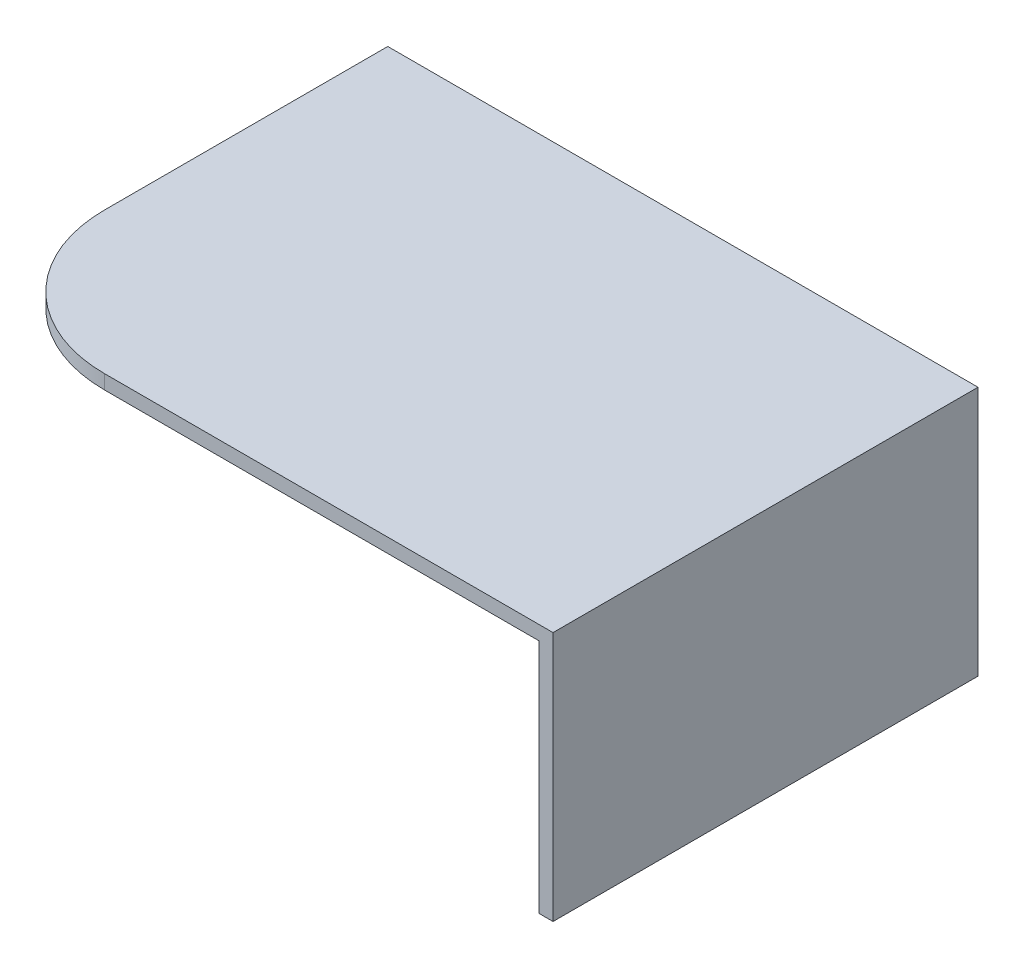
SolidWorks part; units mm, degrees
ref_plane "Front Plane" through (0, 0, 0) normal (0, 0, 1) x (1, 0, 0)
ref_plane "Top Plane" through (0, 0, 0) normal (0, 1, 0) x (1, 0, 0)
ref_plane "Right Plane" through (0, 0, 0) normal (1, 0, 0) x (0, 0, -1)
sketch "Sketch2" plane through (0, 0, 0) normal (0, 0, 1) x (1, 0, 0)
  line L0 (0, 4.05) -> (2.5, 4.05)
  line L1 (0, -4.05) -> (10.5, -4.05)
  line L2 (2.5, 4.05) -> (2.5, 30.95)
  line L3 (2.5, 30.95) -> (-49.5, 30.95)
  line L4 (-49.5, 30.95) -> (-49.5, 33.95)
  line L5 (-49.5, 33.95) -> (10.5, 33.95)
  line L6 (10.5, 33.95) -> (10.5, -4.05)
  line L7 (2.5, 30.95) -> (10.5, 30.95)
  line L8 (10.5, 33.95) -> (75.5, 33.95)
  line L9 (75.5, 33.95) -> (75.5, -19.05)
  line L10 (75.5, -19.05) -> (10.5, -19.05)
  line L11 (10.5, -19.05) -> (10.5, -4.05)
  line L12 (10.5, 30.95) -> (72.5, 30.95)
  line L13 (30.5, 33.95) -> (30.5, 30.95)
  line L14 (72.5, 30.95) -> (72.5, -19.05)
  point P4 (0, 0)
  line B0 (0, -7.95) -> (-2.04, -7.95)
  line B1 (-6.1524, -4.048) -> (-6.1524, 4.048)
  line B2 (-2.04, 7.95) -> (0, 7.95)
  line B3 (0, 7.95) -> (0, -7.95)
  line B4 (-2.04, -7.95) -> (-6.1524, -4.048)
  line B5 (-6.1524, 4.048) -> (-2.04, 7.95)
  line B6 (0, -4.05) -> (0, 4.05) construction
  dimension "D1" = 10.5
  dimension "D2" = 8
  dimension "D3" = 3
  dimension "D4" = 60
  dimension "D5" = 35
  dimension "D6" = 65
  dimension "D7" = 50
  dimension "D8" = 20
  dimension "D9" = 3
sketch_block_instance "Extrusion Profile-1"
sketch_block "Block1" parameters "D1"=8.44, "D2"=2.6, "D3"=6, "D4"=16.7, "D6"=5.6686, "D7"=2.0404, "D8"=8.0963, "D9"=15.9, "D5"=2.4157
extrude "Boss-Extrude1" add sketch "Sketch2" along normal blind 6 contours L0 B3 L1 L6 L7 L2 | B2 B5 B1 B4 B0 B3 region at (-2.7416, 0, 0) region at (6.1459, 12.5429, 0)
extrude "Boss-Extrude2" add sketch "Sketch2<3>" along normal blind 90 contours L3 L7 L6 L5 L4 | L13 L8 L6 | L12 L14 L10 L9 L8 L13 region at (-19.5, 32.45, 0) region at (20.5, 32.45, 0) region at (31.1953, 32.45, 0)
sketch "Sketch2<3>" plane through (0, 0, 0) normal (0, 0, 1) x (1, 0, 0) same geometry as "Sketch2"
extrude "Boss-Extrude3" add sketch "Sketch2<4>" along normal blind 3 contours L6 L11 L10 L9 | L8 L13 L9 region at (41.5, 5.95, 0) region at (31.1953, 32.45, 0)
sketch "Sketch2<4>" plane through (0, 0, 0) normal (0, 0, 1) x (1, 0, 0) same geometry as "Sketch2"
fillet "Fillet1" radius 3 1 edges at (10.5, 13.45, 3)
fillet "Fillet2" radius 3 1 edges at (10.5, 13.45, 6)
fillet "Fillet3" radius 30 1 edges at (-49.5, 32.45, 90)
sketch "Sketch3" plane through (0, 0, 0) normal (0, 0, -1) x (-1, 0, 0)
  line L0 (-2.5, 4.05) -> (-2.5, -4.05)
  line L1 (0, -4.05) -> (-10.5, -4.05) construction
  line L18 (49.5, 33.95) -> (-75.5, 33.95)
  line L19 (-75.5, 33.95) -> (-75.5, -19.05)
  line L20 (-75.5, -19.05) -> (-10.5, -19.05)
  line L21 (-10.5, -19.05) -> (-10.5, -4.05)
  line L22 (-10.5, -4.05) -> (0, -4.05)
  line L23 (0, -4.05) -> (0, -7.95)
  line L24 (0, -7.95) -> (2.04, -7.95)
  line L25 (2.04, -7.95) -> (6.1524, -4.048)
  line L26 (6.1524, -4.048) -> (6.1524, 4.048)
  line L27 (6.1524, 4.048) -> (2.04, 7.95)
  line L28 (2.04, 7.95) -> (0, 7.95)
  line L29 (0, 7.95) -> (0, 4.05)
  line L30 (0, 4.05) -> (-2.5, 4.05)
  line L31 (-2.5, 4.05) -> (-2.5, 30.95)
  line L32 (-2.5, 30.95) -> (49.5, 30.95)
  line L33 (49.5, 30.95) -> (49.5, 33.95)
  line L34 (49.5, 33.95) -> (-75.5, 33.95)
  line L35 (-75.5, 33.95) -> (-75.5, -19.05)
  line L36 (-75.5, -19.05) -> (-10.5, -19.05)
  line L37 (-10.5, -19.05) -> (-10.5, -4.05)
  line L38 (-10.5, -4.05) -> (-2.5, -4.05)
  line L47 (-2.5, 4.05) -> (-2.5, 30.95)
  line L48 (-2.5, 30.95) -> (49.5, 30.95)
  line L49 (49.5, 30.95) -> (49.5, 33.95)
  dimension "D1" = 0
sketch "Sketch4" plane through (0, 0, 0) normal (0, 0, -1) x (-1, 0, 0)
  line L0 (6.1524, 1) -> (6.1524, -1)
  line L1 (6.1524, -4.048) -> (6.1524, 4.048) construction
  line L2 (6.1524, -1) -> (2.1524, -1)
  line L3 (2.1524, -1) -> (2.1524, 1)
  line L4 (2.1524, 1) -> (6.1524, 1)
  point P5 (6.1524, 0)
  dimension "D1" = 2
  dimension "D2" = 4
extrude "Cut-Extrude1" cut sketch "Sketch4" against normal through all
